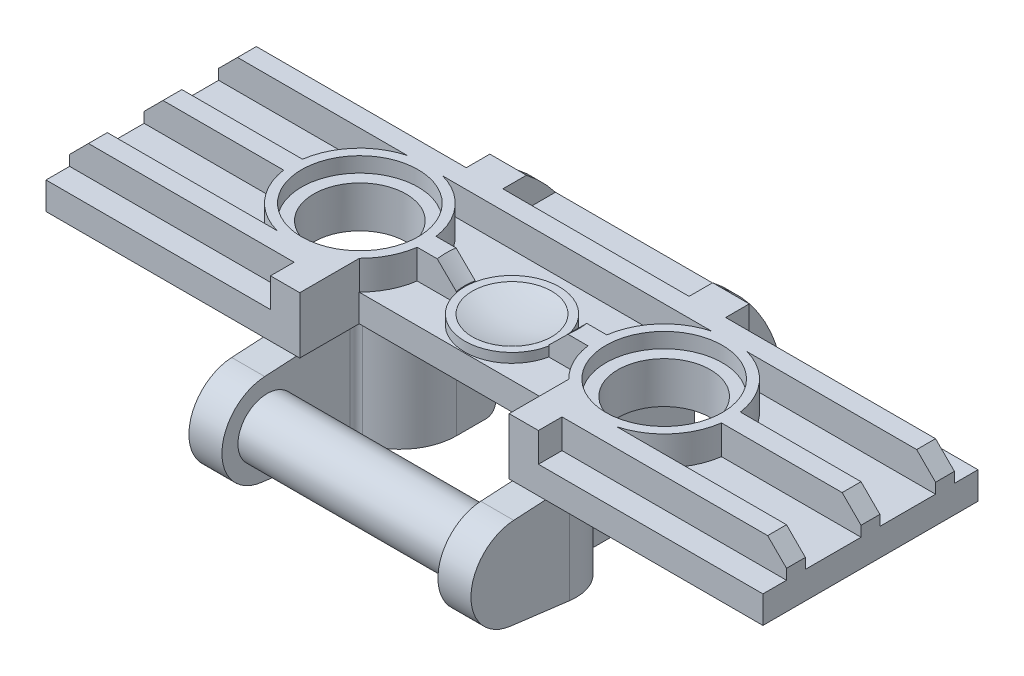
SolidWorks part; units mm, degrees
ref_plane "Front Plane" through (0, 0, 0) normal (0, 0, 1) x (1, 0, 0)
ref_plane "Top Plane" through (0, 0, 0) normal (0, 1, 0) x (1, 0, 0)
ref_plane "Right Plane" through (0, 0, 0) normal (1, 0, 0) x (0, 0, -1)
sketch "Sketch1" plane through (0, 0, 0) normal (0, 1, 0) x (1, 0, 0)
  line L0 (-19, 4.45) -> (-6.875, 4.45)
  line L1 (-7.1, -5.7) -> (-5.55, -5.7)
  line L2 (-19, -4.45) -> (-19, -3.45)
  line L3 (-6.875, 5.7) -> (-4.975, 5.7)
  line L4 (19, -4.45) -> (19, -3.45)
  line L5 (-19, 3.45) -> (-19, 4.45)
  line L6 (-19, -0.5) -> (-19, 0.5)
  line L7 (-19, 3.45) -> (-9.0021, 3.45)
  line L8 (19, 3.45) -> (19, 4.45)
  line L9 (19, -0.5) -> (19, 0.5)
  line L10 (-19, -3.45) -> (-9.0021, -3.45)
  line L11 (19, -3.45) -> (19, -4.45)
  line L12 (19, -4.45) -> (7.1, -4.45)
  line L13 (-19, 0.5) -> (-11.6049, 0.5)
  line L14 (19, 0.5) -> (19, -0.5)
  line L15 (19, -0.5) -> (11.6049, -0.5)
  line L16 (-6.875, 4.45) -> (-6.875, 5.7)
  line L17 (-4.975, 4.45) -> (-4.975, 5.7)
  line L18 (4.975, 4.45) -> (4.975, 5.7)
  line L19 (6.875, 4.45) -> (6.875, 5.7)
  line L20 (-7.1, -4.45) -> (-7.1, -5.7)
  line L21 (-5.55, -2.5407) -> (-5.55, -5.7)
  line L22 (5.55, -2.5407) -> (5.55, -5.7)
  line L23 (7.1, -4.45) -> (7.1, -5.7)
  line L24 (5.55, -5.7) -> (7.1, -5.7)
  line L25 (-7.1, -4.45) -> (-19, -4.45)
  line L27 (-11.6049, -0.5) -> (-19, -0.5)
  line L28 (-4.5251, 0.5) -> (-2.4495, 0.5)
  line L29 (-7.1279, 3.45) -> (7.1279, 3.45)
  line L30 (-4.975, 4.45) -> (4.975, 4.45)
  line L31 (4.975, 5.7) -> (6.875, 5.7)
  line L32 (9.0021, -3.45) -> (19, -3.45)
  line L33 (4.5251, -0.5) -> (2.4495, -0.5)
  line L34 (11.6049, 0.5) -> (19, 0.5)
  line L35 (9.0021, 3.45) -> (19, 3.45)
  line L36 (-2.4495, -0.5) -> (-4.5251, -0.5)
  line L37 (2.4495, 0.5) -> (4.5251, 0.5)
  line L38 (6.875, 4.45) -> (19, 4.45)
  circle A1 centre (-8.065, 0) radius 3.0875
  circle A2 centre (8.065, 0) radius 3.0875
  arc A3 (9.0021, -3.45) -> (11.6049, -0.5) centre (8.065, 0) ccw
  arc A4 (-5.55, -2.5407) -> (-4.5251, -0.5) centre (-8.065, 0) ccw
  arc A5 (2.4495, -0.5) -> (2.4495, 0.5) centre (0, 0) ccw
  arc A6 (-4.5251, 0.5) -> (-7.1279, 3.45) centre (-8.065, 0) ccw
  arc A7 (-9.0021, 3.45) -> (-11.6049, 0.5) centre (-8.065, 0) ccw
  arc A8 (4.5251, -0.5) -> (5.55, -2.5407) centre (8.065, 0) ccw
  arc A9 (11.6049, 0.5) -> (9.0021, 3.45) centre (8.065, 0) ccw
  arc A10 (7.1279, 3.45) -> (4.5251, 0.5) centre (8.065, 0) ccw
  arc A11 (-11.6049, -0.5) -> (-9.0021, -3.45) centre (-8.065, 0) ccw
  arc A12 (-2.4495, 0.5) -> (-2.4495, -0.5) centre (0, 0) ccw
  point P0 (0, 0)
  dimension "D3" = 16.13
  dimension "D5" = 6.175
  dimension "D6" = 7.15
  dimension "D7" = 6.175
  dimension "D8" = 7.15
  dimension "D9" = 1.25
  dimension "D10" = 1
  dimension "D11" = 2.95
  dimension "D12" = 1
  dimension "D13" = 2.95
  dimension "D14" = 1
  dimension "D15" = 13.75
  dimension "D16" = 9.95
  dimension "D21" = 14.2
  dimension "D22" = 7.1
  dimension "D23" = 11.1
  dimension "D24" = 5.55
sketch "Sketch2" plane through (0, 0, 0) normal (0, 1, 0) x (1, 0, 0)
  line L1 (-19, -5.7) -> (19, -5.7)
  line L2 (-19, -5.7) -> (-19, 5.7)
  line L3 (-19, 5.7) -> (19, 5.7)
  line L4 (19, -5.7) -> (19, 5.7)
  line L5 (-19, -5.7) -> (19, 5.7) construction
  line L6 (-19, 5.7) -> (19, -5.7) construction
  point P0 (0, 0)
  dimension "D1" = 38
  dimension "D2" = 11.4
extrude "Boss-Extrude1" add sketch "Sketch2" against normal blind 1.45
extrude "Boss-Extrude2" add sketch "Sketch1" along normal blind 1.55 contours A12 L28 A6 L29 A10 L37 A5 L33 A8 L22 L24 L23 L12 L4 L32 A3 L15 L9 L34 A9 L35 L8 L38 L19 L31 L18 L30 L17 L3 L16 L0 L5 L7 A7 L13 L6 L27 A11 L10 L2 L25 L20 L1 L21 A4 L36 A2 A1 | A1 | A2 region at (-12.9375, 0, -4.0533) region at (-8.065, 0, 0) region at (8.065, 0, 0)
sketch "Sketch4" plane through (0, 0, 0) normal (0, 1, 0) x (1, 0, 0)
  line L0 (5.55, -2.5407) -> (5.55, -5.7) construction
  line L1 (-5.55, -5.7) -> (5.55, -5.7)
  line L2 (-5.55, -5.7) -> (-5.55, -2.55)
  line L3 (-5.55, -2.55) -> (5.55, -2.55)
  line L4 (5.55, -5.7) -> (5.55, -2.55)
  dimension "D1" = 3.15
extrude "Cut-Extrude1" cut sketch "Sketch4" against normal blind 1.55
sketch "Sketch5" plane through (0, 0, 0) normal (0, 1, 0) x (1, 0, 0)
  circle A0 centre (0, 0) radius 2.5
  arc M6 (2.4495, -0.5) -> (2.4495, 0.5) centre (0, 0) ccw
  arc M12 (-2.4495, 0.5) -> (-2.4495, -0.5) centre (0, 0) ccw
extrude "Boss-Extrude3" add sketch "Sketch5" along normal blind 0.5 contours A0 M6 M12 region at (0, 0, 0)
sketch "Sketch6" plane through (0, -1.45, 0) normal (0, -1, 0) x (1, 0, 0)
  line L1 (-5.425, -4.25) -> (-3.325, -4.25)
  line L2 (-5.425, -4.25) -> (-5.425, 2.55)
  line L3 (-5.425, 2.55) -> (-3.325, 2.55)
  line L4 (-3.325, -4.25) -> (-3.325, 2.55)
  line L6 (3.325, -4.25) -> (5.425, -4.25)
  line L7 (3.325, -4.25) -> (3.325, 2.55)
  line L8 (3.325, 2.55) -> (5.425, 2.55)
  line L9 (5.425, -4.25) -> (5.425, 2.55)
  dimension "D1" = 6.8
  dimension "D2" = 2.1
  dimension "D3" = 2.1
  dimension "D4" = 6.8
  dimension "D5" = 10.85
  dimension "D6" = 5.425
extrude "Boss-Extrude4" add sketch "Sketch6" along normal blind 5.5
sketch "Sketch8" plane through (5.425, 0, 0) normal (1, 0, 0) x (0, 0, -1)
  line L0 (4.45, 1.55) -> (5.7, 1.55) construction
  line L1 (2.2086, -5.85) -> (4.0412, -5.85)
  line L2 (3.45, 1.55) -> (0.5, 1.55) construction
  line L3 (-2.55, -6.95) -> (-2.55, -1.45) construction
  line L4 (7.4624, -5.85) -> (8.6353, -5.85)
  line L5 (8.9974, -4.5881) -> (8.6353, -5.85)
  line L6 (5.7, 1.55) -> (3.8245, 1.55)
  line L7 (3.45, 1.55) -> (4.45, 1.55) construction
  line L8 (3.8245, 1.55) -> (2.2086, -5.85)
  arc A0 (6.9997, -4.8637) -> (4.502, -4.8657) centre (5.75, -3.825) ccw
  arc A2 (8.9974, -4.5881) -> (5.7, 1.55) centre (0.3825, -5.2613) ccw
  arc A3 (6.9997, -4.8637) -> (7.4624, -5.85) centre (7.4624, -5.2483) ccw
  arc A4 (4.0412, -5.85) -> (4.502, -4.8657) centre (4.0412, -5.25) ccw
  line M1 (4.25, -1.45) -> (-2.55, -1.45)
  line M4 (4.25, -6.95) -> (4.25, -1.45)
  dimension "D1" = 5.375
  dimension "D2" = 3.25
  dimension "D5" = 8.3
  dimension "D4" = 7.4
extrude "Boss-Extrude5" add sketch "Sketch8" along direction (1, 0, 0) on the side against the normal blind 2.1 contours A0 A3 L4 L5 A2 L6 L8 M1 M4 | A4 A0 M4 region at (5.425, -1.6376, -6.2657) region at (5.425, -5.2149, -4.4061)
sketch "Sketch10" plane through (5.425, 0, 0) normal (1, 0, 0) x (0, 0, -1)
  line L0 (4.25, -6.95) -> (4.25, -5.8125) construction
  line L1 (4.25, -6.95) -> (2.45, -6.95)
  line L2 (4.25, -6.95) -> (4.25, -5.8125)
  line L3 (4.25, -5.8125) -> (2.45, -5.8125)
  line L4 (2.45, -6.95) -> (2.45, -5.8125)
  arc A0 (4.25, -5.8125) -> (4.502, -4.8657) centre (4.0412, -5.25) ccw construction
  dimension "D1" = 1.8
extrude "Cut-Extrude2" cut sketch "Sketch10" against normal blind 13.5
mirror "Mirror2" about plane through (0, 0, 0) normal (1, 0, 0) of "Boss-Extrude5"
sketch "Sketch11" plane through (0, 0, -5.7) normal (0, 0, -1) x (-1, 0, 0)
  line L1 (-3.325, 0) -> (3.325, 0)
  line L2 (-3.325, 0) -> (-3.325, -1.45)
  line L3 (-3.325, -1.45) -> (3.325, -1.45)
  line L4 (3.325, 0) -> (3.325, -1.45)
extrude "Boss-Extrude6" add sketch "Sketch11" along normal up to surface (1.5373 mm away) up to face at (-4.375, -1.3455, -7.6718)
sketch "Sketch13" plane through (0, 0, 0) normal (0, 1, 0) x (1, 0, 0)
  line L1 (-4.9349, 4.45) -> (-3.325, 4.45)
  line L2 (-4.9349, 4.45) -> (-4.9349, 7.2373)
  line L3 (-4.9349, 7.2373) -> (-3.325, 7.2373)
  line L4 (-3.325, 4.45) -> (-3.325, 7.2373)
  line L5 (-3.325, 4.45) -> (-3.325, 7.2373) construction
  line L7 (3.325, 4.45) -> (3.325, 8.3693)
  line L8 (4.9349, 8.3693) -> (3.325, 8.3693)
  line L9 (4.9349, 4.45) -> (4.9349, 8.3693)
  line L10 (4.9349, 4.45) -> (3.325, 4.45)
extrude "Cut-Extrude3" cut sketch "Sketch13" along normal blind 4.25
ref_plane "Plane1" through (7.475, 0, 0) normal (1, 0, 0) x (0, 0, -1)
sketch "Sketch14" plane through (7.475, 0, 0) normal (1, 0, 0) x (0, 0, -1)
  line L1 (-5.7, -1.45) -> (-5.7, 0) construction
  line L2 (-2.55, -6.95) -> (-7.5498, -6.3204)
  line L3 (-5.7, -1.45) -> (-7.3832, -1.5435)
  line L4 (-5.7, -1.45) -> (-2.55, -1.45)
  line L6 (-2.55, -6.95) -> (-1.9898, -6.95)
  line L7 (2.45, -6.95) -> (-2.55, -6.95) construction
  line L8 (-1.9898, -6.95) -> (-1.9898, -1.45)
  line L9 (5.7, -1.45) -> (-2.55, -1.45) construction
  line L10 (-1.9898, -1.45) -> (-2.55, -1.45)
  circle A0 centre (-7.25, -3.9395) radius 1.55
  circle A1 centre (-7.25, -3.9395) radius 2.3997
  dimension "D1" = 3.1
  dimension "D2" = 1.55
extrude "Boss-Extrude9" add sketch "Sketch14" against normal blind 1.75 contours A1 L2 L6 L8 L10 L4 L3 | A1 A0 | A0 region at (7.475, -4.1453, 3.7413) region at (7.475, -3.8582, 9.5804) region at (7.475, -3.9395, 7.25)
mirror "Mirror3" about plane through (0, 0, 0) normal (1, 0, 0) of "Boss-Extrude9"
sketch "Sketch15" plane through (-7.475, 0, 0) normal (-1, 0, 0) x (0, 0, 1)
  circle A0 centre (7.25, -3.9395) radius 1.55
extrude "Boss-Extrude10" add sketch "Sketch15" against normal up to surface (13.2 mm away) up to face at (5.725, -4.098, 4.8907)
sketch "Sketch17" plane through (0, 0, 0) normal (0, 0, 1) x (1, 0, 0)
  line L0 (2.1, 0.5) -> (2.1, 0.7109)
  line L4 (2.1, 0.7109) -> (0, 1.0536)
  line L5 (0, 1.0536) -> (0, 0.1838)
  arc A0 (0, 0.1838) -> (2.1, 0.5) centre (0, 7.3155) ccw
revolve "Cut-Revolve4" cut sketch "Sketch17" angle 360 about L5
sketch "Sketch19" plane through (0, -6.95, 0) normal (0, -1, 0) x (1, 0, 0)
  line L0 (3.325, 2.55) -> (3.325, -2.45) construction
  line L1 (3.325, 1.5687) -> (7.475, 1.5687)
  line L2 (3.325, 1.5687) -> (3.325, 2.55)
  line L3 (3.325, 2.55) -> (7.475, 2.55)
  line L4 (7.475, 1.5687) -> (7.475, 2.55)
  line L5 (7.475, 1.9898) -> (7.475, 2.55) construction
  line L6 (7.475, 5.7) -> (7.475, 2.55) construction
extrude "Boss-Extrude11" add sketch "Sketch19" against normal up to surface (5.5 mm away) up to face at (8.6288, -1.45, 2.048)
mirror "Mirror4" about plane through (0, 0, 0) normal (1, 0, 0) of "Boss-Extrude11"
fillet "Fillet1" radius 3 4 edges at (7.475, -4.2, 1.5687) (3.325, -4.2, 2.55) (-7.475, -4.2, 1.5687)
fillet "Fillet2" radius 0.5 6 edges at (-4.375, -5.85, -8.6353) (4.375, -5.85, -8.6353) (-4.375, -4.5881, -8.9974) (4.375, -4.5881, -8.9974) (-4.375, -6.95, -2.45) (4.375, -6.95, -2.45)
chamfer "Chamfer1" distance 1 angle 45 8 edges at (-2.5, 1.55, 0) (-19, 1.55, -3.95) (-19, 1.55, 0) (-19, 1.55, 3.95) (19, 1.55, 3.95) (19, 1.55, -3.95) (19, 1.55, 0) (2.5, 1.55, 0)
sketch "Sketch20" plane through (0, 0, 0) normal (0, 1, 0) x (1, 0, 0)
  circle A0 centre (-8.065, 0) radius 2.45
  circle A1 centre (8.065, 0) radius 2.45
extrude "Cut-Extrude4" cut sketch "Sketch20" against normal mid plane 6.25
sketch "Sketch21" plane through (0, 1.55, 0) normal (0, 1, 0) x (1, 0, 0)
  circle A0 centre (-8.065, 0) radius 3.0875
  circle A1 centre (8.065, 0) radius 3.0875
extrude "Cut-Extrude5" cut sketch "Sketch21" against normal blind 0.8
fillet "Fillet5" radius 0.4 4 edges at (5.425, -4.2, 1.5687) (-5.425, -4.2, 1.5687) (-5.725, -4.2, 2.55) (5.725, -4.2, 2.55)
sketch "Sketch24" plane through (0, 0, 0) normal (1, 0, 0) x (0, 0, -1)
  spline S0 degree 3 poles (-15.5824, -43.1643) (-42.1661, -41.4209) (-61.7442, -44.5395) (-73.228, -63.1066) (-62.9076, -82.3775) (-47.264, -86.1624) (-31.611, -85.1652) (-10.8872, -85.6051) (24.0014, -85.3658) (66.8183, -85.6547) (102.0338, -85.1863) (121.4454, -85.5973) (133.2803, -83.9015) (145.3548, -68.7468) (138.9241, -47.8953) (120.7618, -41.0737) (103.9135, -42.7902) (84.272, -42.3241) (57.4028, -42.5769) (20.8652, -42.2473) (-15.5824, -43.1643) (-42.1661, -41.4209) (-61.7442, -44.5395) knots -0.233884 -0.150141 -0.054947 0 0.02139 0.069617 0.112176 0.139845 0.168415 0.213224 0.272824 0.39271 0.488395 0.49898 0.517604 0.563837 0.601065 0.640126 0.677094 0.710207 0.766116 0.849859 0.945053 1 1.02139 1.069617 1.112176 only from (-47.4535, -42.472) to (-47.4535, -42.472)
